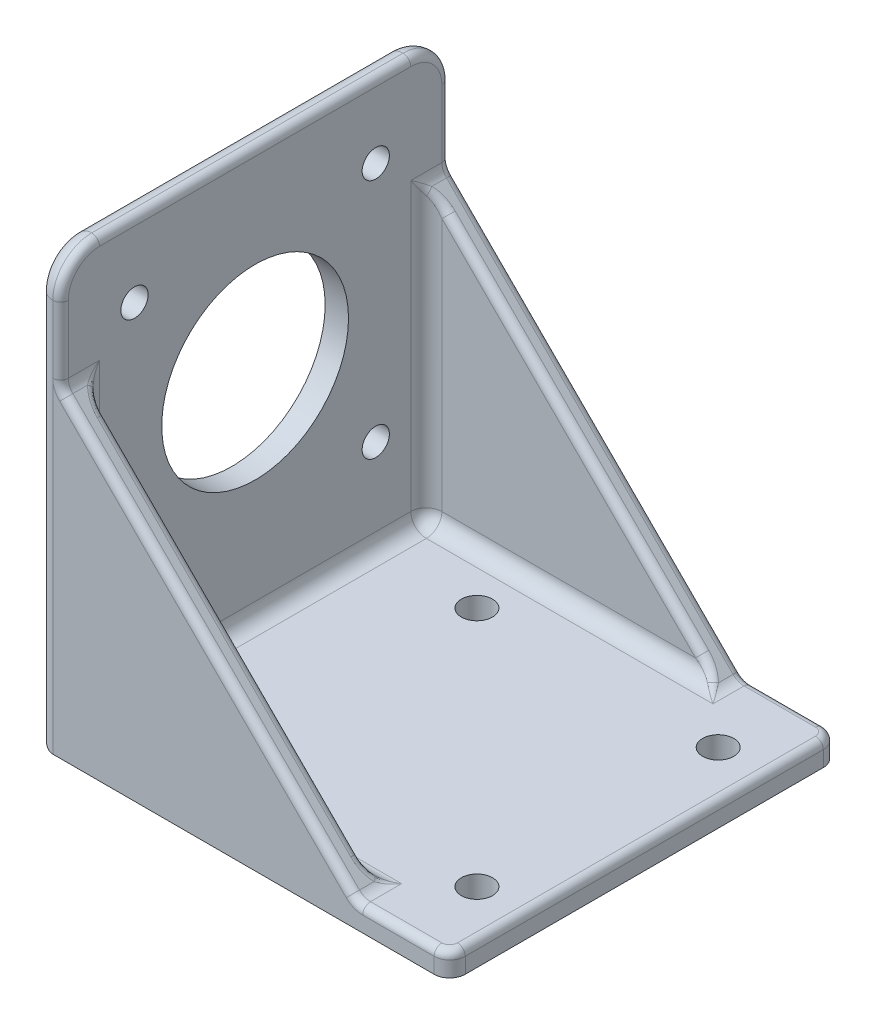
SolidWorks part; units mm, degrees
ref_plane "前视基准面" through (0, 0, 0) normal (0, 0, 1) x (1, 0, 0)
ref_plane "上视基准面" through (0, 0, 0) normal (0, 1, 0) x (1, 0, 0)
ref_plane "右视基准面" through (0, 0, 0) normal (1, 0, 0) x (0, 0, -1)
sketch "草图2" plane through (0, 0, 0) normal (1, 0, 0) x (0, 0, -1)
  line L1 (-25, -27.75) -> (25, -27.75)
  line L2 (-25, -27.75) -> (-25, 22.75)
  line L3 (-20, 27.75) -> (20, 27.75)
  line L4 (25, -27.75) -> (25, 22.75)
  line L5 (-25, -27.75) -> (25, 27.75) construction
  line L6 (-25, 27.75) -> (25, -27.75) construction
  circle A0 centre (15.5, 18.25) radius 1.75
  arc A4 (20, 27.75) -> (25, 22.75) centre (20, 22.75) cw
  arc A5 (-25, 22.75) -> (-20, 27.75) centre (-20, 22.75) cw
  circle A7 centre (0, 2.75) radius 12
  circle A8 centre (-15.5, 18.25) radius 1.75
  circle A9 centre (-15.5, -12.75) radius 1.75
  circle A10 centre (15.5, -12.75) radius 1.75
  point P0 (0, 0)
  point P5 (0, 0)
  dimension "D3" = 9.5
  dimension "D4" = 3.5
  dimension "D5" = 5
  dimension "D6" = 30.5
  dimension "D8" = 24
  dimension "D1" = 50
  dimension "D2" = 55.5
  dimension "D7" = 46
  dimension "D9" = 2
  dimension "D10" = 2
extrude "凸台-拉伸1" add sketch "草图2" along normal blind 2 and the other way blind 1
sketch "草图4" plane through (0, 0, 0) normal (1, 0, 0) x (0, 0, -1)
  line L0 (-25, 22.75) -> (-25, -27.75) construction
  line L1 (25, -27.75) -> (-25, -27.75)
  line L2 (25, -27.75) -> (25, -24.75)
  line L3 (25, -24.75) -> (-25, -24.75)
  line L4 (-25, -27.75) -> (-25, -24.75)
  dimension "D1" = 3
extrude "凸台-拉伸2" add sketch "草图4" along normal blind 52
ref_plane "基准面4" through (0, 0, 25) normal (0, 0, 1) x (1, 0, 0)
sketch "草图5" plane through (0, 0, 25) normal (0, 0, 1) x (1, 0, 0)
  line L0 (2, 13.25) -> (40, -24.75)
  line L1 (2, 22.75) -> (2, -24.75) construction
  line L2 (52, -24.75) -> (2, -24.75) construction
  line L3 (2, 13.25) -> (2, -24.75)
  line L4 (2, -24.75) -> (40, -24.75)
  dimension "D1" = 38
  dimension "D2" = 38
extrude "凸台-拉伸3" add sketch "草图5" against normal blind 3
ref_plane "基准面5" through (0, 0, -25) normal (0, 0, 1) x (1, 0, 0)
sketch "草图6" plane through (0, 0, -25) normal (0, 0, 1) x (1, 0, 0)
  line L3 (40, -24.75) -> (2, 13.25)
  line L4 (2, -24.75) -> (40, -24.75)
  line L5 (2, 13.25) -> (2, -24.75)
  line L6 (40, -24.75) -> (2, 13.25)
  line L7 (2, -24.75) -> (40, -24.75)
  line L8 (2, 13.25) -> (2, -24.75)
  dimension "D1" = 0
extrude "凸台-拉伸4" add sketch "草图6" along normal blind 3
sketch "草图7" plane through (0, 0, 0) normal (0, 1, 0) x (1, 0, 0)
  line L0 (-29.15, -25) -> (29.15, -25) construction
  line L1 (15, -15.5) -> (46, -15.5)
  line L2 (15, -15.5) -> (15, 15.5)
  line L3 (15, 15.5) -> (46, 15.5)
  line L4 (46, -15.5) -> (46, 15.5)
  line L5 (15, -15.5) -> (46, 15.5) construction
  line L6 (15, 15.5) -> (46, -15.5) construction
  circle A0 centre (15, 15.5) radius 2
  circle A1 centre (46, 15.5) radius 2
  circle A2 centre (46, -15.5) radius 2
  circle A3 centre (15, -15.5) radius 2
  point P0 (30.5, 0)
  dimension "D3" = 4
  dimension "D1" = 31
  dimension "D2" = 31
  dimension "D6" = 15
  dimension "D7" = 9.5
  dimension "D4" = 2
  dimension "D5" = 2
extrude "切除-拉伸2" cut sketch "草图7" against normal blind 30 contours L1 A2 L4 | L4 A2 L1 | L4 A1 L3 | L3 A1 L4 | L2 A0 L3 | L3 A0 L2 | L1 A3 L2 | L2 A3 L1 region at (15.8488, 0, 14.6512) region at (14.7171, 0, 15.7829) region at (45.1512, 0, 14.6512) region at (46.2829, 0, 15.7829) region at (14.7171, 0, -15.7829) region at (15.8488, 0, -14.6512) region at (45.1512, 0, -14.6512) region at (46.2829, 0, -15.7829)
fillet "圆角2" radius 2 1 edges at (52, -26.25, 25)
fillet "圆角3" radius 2 1 edges at (52, -26.25, -25)
fillet "圆角7" radius 2 9 edges at (2, -5.75, -22) (21, -24.75, -22) (21, -24.75, 22) (2, -5.75, 22) (2, -24.75, 0) (2, 13.25, -23.5) (40, -24.75, -23.5) (40, -24.75, 23.5) (2, 13.25, 23.5)
fillet "圆角8" radius 2 6 edges at (-1, -2.5, -25) (-1, 26.2855, -23.5355) (-1, -2.5, 25) (-1, 26.2855, 23.5355) (-1, -27.75, 0) (-1, 27.75, 0)
fillet "圆角9" radius 1 26 edges at (40.0631, -24.5978, 20.7654) (38.7654, -23.5154, 21.8478) (2.1522, 13.3131, 20.7654) (3.2346, 12.0154, 21.8478) (21, -5.75, 22) (40.0631, -24.5978, 25) (45.4142, -24.75, 25) (51.4142, -24.75, 24.4142) (52, -24.75, 0) (51.4142, -24.75, -24.4142) (45.4142, -24.75, -25) (40.0631, -24.5978, -25) (21, -5.75, -25) (2.1522, 13.3131, -25) (2, 18.4142, -25) (2, 26.2855, -23.5355) (2, 27.75, 0) (2, 26.2855, 23.5355) (2, 18.4142, 25) (2.1522, 13.3131, 25) (40.0631, -24.5978, -20.7654) (38.7654, -23.5154, -21.8478) (2.1522, 13.3131, -20.7654) (3.2346, 12.0154, -21.8478) (21, -5.75, 25) (21, -5.75, -22)
